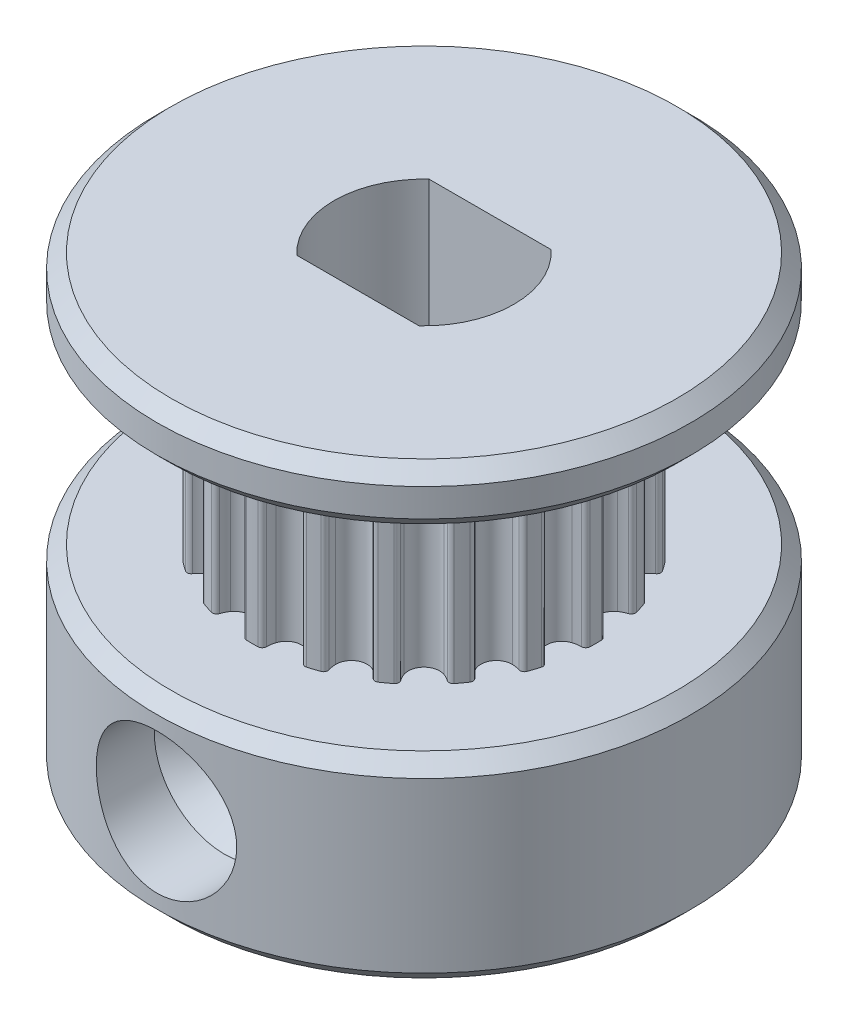
SolidWorks part; units mm, degrees
other "Markup1"
sketch "Sketch11" plane through (-10, 5.5, 10) normal (-0.2341, 0.0958, 0.9675) x (0.972, 0, 0.2351)
sketch "Sketch12" plane through (-9.5, 5.5, 9.5) normal (-0.2341, 0.0958, 0.9675) x (0.972, 0, 0.2351)
ref_plane "Front Plane" through (0, 0, 0) normal (0, 0, 1) x (1, 0, 0)
ref_plane "Top Plane" through (0, 0, 0) normal (0, 1, 0) x (1, 0, 0)
ref_plane "Right Plane" through (0, 0, 0) normal (1, 0, 0) x (0, 0, -1)
sketch "Sketch1" plane through (0, 0, 0) normal (0, 1, 0) x (1, 0, 0)
  line L0 (0, 0) -> (0, 6.3662) construction
  line L2 (0, 0) -> (0.9236, 5.8314) construction
  line L3 (0, 0) -> (1.4053, 6.2092) construction
  line L4 (1.3492, 5.9614) -> (1.2615, 5.4076) construction
  circle A0 centre (0, 0) radius 6.3662
  arc A1 (0.3928, 5.6692) -> (0.8368, 5.2832) centre (0.9236, 5.8314) ccw
  arc A2 (0.3492, 5.9592) -> (0.2042, 6.1088) centre (0.1992, 5.9589) ccw
  arc A3 (0.3492, 5.9592) -> (0.3928, 5.6692) centre (1.3492, 5.9614) ccw
  arc A4 (-0.3928, 5.6692) -> (-0.8368, 5.2832) centre (-0.9236, 5.8314) cw
  arc A5 (0.2042, 6.1088) -> (-0.2042, 6.1088) centre (0, 0) ccw
  arc A6 (-0.3492, 5.9592) -> (-0.3928, 5.6692) centre (-1.3492, 5.9614) cw
  arc A7 (-0.3492, 5.9592) -> (-0.2042, 6.1088) centre (-0.1992, 5.9589) cw
  arc A8 (1.3783, 5.5132) -> (0.8368, 5.2832) centre (0.9236, 5.8314) cw
  arc A9 (1.5094, 5.7754) -> (1.3783, 5.5132) centre (0.559, 6.0866) cw
  arc A10 (1.5094, 5.7754) -> (1.6935, 5.8729) centre (1.652, 5.7288) cw
  arc A11 (2.0819, 5.7467) -> (1.6935, 5.8729) centre (0, 0) ccw
  arc A12 (2.1736, 5.5596) -> (2.0819, 5.7467) centre (2.0308, 5.6057) ccw
  arc A13 (2.1736, 5.5596) -> (2.1255, 5.2704) centre (3.1253, 5.2527) ccw
  arc A14 (2.1255, 5.2704) -> (2.4284, 4.7661) centre (2.6804, 5.2606) ccw
  arc A15 (3.0145, 4.8174) -> (2.4284, 4.7661) centre (2.6804, 5.2606) cw
  arc A16 (3.2202, 5.0263) -> (3.0145, 4.8174) centre (2.4125, 5.6159) cw
  arc A17 (3.2202, 5.0263) -> (3.4255, 5.0621) centre (3.3414, 4.9379) cw
  arc A18 (3.7559, 4.8221) -> (3.4255, 5.0621) centre (0, 0) ccw
  arc A19 (3.7852, 4.6159) -> (3.7559, 4.8221) centre (3.6637, 4.7037) ccw
  arc A20 (3.7852, 4.6159) -> (3.6501, 4.3556) centre (4.5956, 4.0299) ccw
  arc A21 (3.6501, 4.3556) -> (3.7824, 3.7824) centre (4.1748, 4.1748) ccw
  arc A22 (4.3556, 3.6501) -> (3.7824, 3.7824) centre (4.1748, 4.1748) cw
  arc A23 (4.6159, 3.7852) -> (4.3556, 3.6501) centre (4.0299, 4.5956) cw
  arc A24 (4.6159, 3.7852) -> (4.8221, 3.7559) centre (4.7037, 3.6637) cw
  arc A25 (5.0621, 3.4255) -> (4.8221, 3.7559) centre (0, 0) ccw
  arc A26 (5.0263, 3.2202) -> (5.0621, 3.4255) centre (4.9379, 3.3414) ccw
  arc A27 (5.0263, 3.2202) -> (4.8174, 3.0145) centre (5.6159, 2.4125) ccw
  arc A28 (4.8174, 3.0145) -> (4.7661, 2.4284) centre (5.2606, 2.6804) ccw
  arc A29 (5.2704, 2.1255) -> (4.7661, 2.4284) centre (5.2606, 2.6804) cw
  arc A30 (5.5596, 2.1736) -> (5.2704, 2.1255) centre (5.2527, 3.1253) cw
  arc A31 (5.5596, 2.1736) -> (5.7467, 2.0819) centre (5.6057, 2.0308) cw
  arc A32 (5.8729, 1.6935) -> (5.7467, 2.0819) centre (0, 0) ccw
  arc A33 (5.7754, 1.5094) -> (5.8729, 1.6935) centre (5.7288, 1.652) ccw
  arc A34 (5.7754, 1.5094) -> (5.5132, 1.3783) centre (6.0866, 0.559) ccw
  arc A35 (5.5132, 1.3783) -> (5.2832, 0.8368) centre (5.8314, 0.9236) ccw
  arc A36 (5.6692, 0.3928) -> (5.2832, 0.8368) centre (5.8314, 0.9236) cw
  arc A37 (5.9592, 0.3492) -> (5.6692, 0.3928) centre (5.9614, 1.3492) cw
  arc A38 (5.9592, 0.3492) -> (6.1088, 0.2042) centre (5.9589, 0.1992) cw
  arc A39 (6.1088, -0.2042) -> (6.1088, 0.2042) centre (0, 0) ccw
  arc A40 (5.9592, -0.3492) -> (6.1088, -0.2042) centre (5.9589, -0.1992) ccw
  arc A41 (5.9592, -0.3492) -> (5.6692, -0.3928) centre (5.9614, -1.3492) ccw
  arc A42 (5.6692, -0.3928) -> (5.2832, -0.8368) centre (5.8314, -0.9236) ccw
  arc A43 (5.5132, -1.3783) -> (5.2832, -0.8368) centre (5.8314, -0.9236) cw
  arc A44 (5.7754, -1.5094) -> (5.5132, -1.3783) centre (6.0866, -0.559) cw
  arc A45 (5.7754, -1.5094) -> (5.8729, -1.6935) centre (5.7288, -1.652) cw
  arc A46 (5.7467, -2.0819) -> (5.8729, -1.6935) centre (0, 0) ccw
  arc A47 (5.5596, -2.1736) -> (5.7467, -2.0819) centre (5.6057, -2.0308) ccw
  arc A48 (5.5596, -2.1736) -> (5.2704, -2.1255) centre (5.2527, -3.1253) ccw
  arc A49 (5.2704, -2.1255) -> (4.7661, -2.4284) centre (5.2606, -2.6804) ccw
  arc A50 (4.8174, -3.0145) -> (4.7661, -2.4284) centre (5.2606, -2.6804) cw
  arc A51 (5.0263, -3.2202) -> (4.8174, -3.0145) centre (5.6159, -2.4125) cw
  arc A52 (5.0263, -3.2202) -> (5.0621, -3.4255) centre (4.9379, -3.3414) cw
  arc A53 (4.8221, -3.7559) -> (5.0621, -3.4255) centre (0, 0) ccw
  arc A54 (4.6159, -3.7852) -> (4.8221, -3.7559) centre (4.7037, -3.6637) ccw
  arc A55 (4.6159, -3.7852) -> (4.3556, -3.6501) centre (4.0299, -4.5956) ccw
  arc A56 (4.3556, -3.6501) -> (3.7824, -3.7824) centre (4.1748, -4.1748) ccw
  arc A57 (3.6501, -4.3556) -> (3.7824, -3.7824) centre (4.1748, -4.1748) cw
  arc A58 (3.7852, -4.6159) -> (3.6501, -4.3556) centre (4.5956, -4.0299) cw
  arc A59 (3.7852, -4.6159) -> (3.7559, -4.8221) centre (3.6637, -4.7037) cw
  arc A60 (3.4255, -5.0621) -> (3.7559, -4.8221) centre (0, 0) ccw
  arc A61 (3.2202, -5.0263) -> (3.4255, -5.0621) centre (3.3414, -4.9379) ccw
  arc A62 (3.2202, -5.0263) -> (3.0145, -4.8174) centre (2.4125, -5.6159) ccw
  arc A63 (3.0145, -4.8174) -> (2.4284, -4.7661) centre (2.6804, -5.2606) ccw
  arc A64 (2.1255, -5.2704) -> (2.4284, -4.7661) centre (2.6804, -5.2606) cw
  arc A65 (2.1736, -5.5596) -> (2.1255, -5.2704) centre (3.1253, -5.2527) cw
  arc A66 (2.1736, -5.5596) -> (2.0819, -5.7467) centre (2.0308, -5.6057) cw
  arc A67 (1.6935, -5.8729) -> (2.0819, -5.7467) centre (0, 0) ccw
  arc A68 (1.5094, -5.7754) -> (1.6935, -5.8729) centre (1.652, -5.7288) ccw
  arc A69 (1.5094, -5.7754) -> (1.3783, -5.5132) centre (0.559, -6.0866) ccw
  arc A70 (1.3783, -5.5132) -> (0.8368, -5.2832) centre (0.9236, -5.8314) ccw
  arc A71 (0.3928, -5.6692) -> (0.8368, -5.2832) centre (0.9236, -5.8314) cw
  arc A72 (0.3492, -5.9592) -> (0.3928, -5.6692) centre (1.3492, -5.9614) cw
  arc A73 (0.3492, -5.9592) -> (0.2042, -6.1088) centre (0.1992, -5.9589) cw
  arc A74 (-0.2042, -6.1088) -> (0.2042, -6.1088) centre (0, 0) ccw
  arc A75 (-0.3492, -5.9592) -> (-0.2042, -6.1088) centre (-0.1992, -5.9589) ccw
  arc A76 (-0.3492, -5.9592) -> (-0.3928, -5.6692) centre (-1.3492, -5.9614) ccw
  arc A77 (-0.3928, -5.6692) -> (-0.8368, -5.2832) centre (-0.9236, -5.8314) ccw
  arc A78 (-1.3783, -5.5132) -> (-0.8368, -5.2832) centre (-0.9236, -5.8314) cw
  arc A79 (-1.5094, -5.7754) -> (-1.3783, -5.5132) centre (-0.559, -6.0866) cw
  arc A80 (-1.5094, -5.7754) -> (-1.6935, -5.8729) centre (-1.652, -5.7288) cw
  arc A81 (-2.0819, -5.7467) -> (-1.6935, -5.8729) centre (0, 0) ccw
  arc A82 (-2.1736, -5.5596) -> (-2.0819, -5.7467) centre (-2.0308, -5.6057) ccw
  arc A83 (-2.1736, -5.5596) -> (-2.1255, -5.2704) centre (-3.1253, -5.2527) ccw
  arc A84 (-2.1255, -5.2704) -> (-2.4284, -4.7661) centre (-2.6804, -5.2606) ccw
  arc A85 (-3.0145, -4.8174) -> (-2.4284, -4.7661) centre (-2.6804, -5.2606) cw
  arc A86 (-3.2202, -5.0263) -> (-3.0145, -4.8174) centre (-2.4125, -5.6159) cw
  arc A87 (-3.2202, -5.0263) -> (-3.4255, -5.0621) centre (-3.3414, -4.9379) cw
  arc A88 (-3.7559, -4.8221) -> (-3.4255, -5.0621) centre (0, 0) ccw
  arc A89 (-3.7852, -4.6159) -> (-3.7559, -4.8221) centre (-3.6637, -4.7037) ccw
  arc A90 (-3.7852, -4.6159) -> (-3.6501, -4.3556) centre (-4.5956, -4.0299) ccw
  arc A91 (-3.6501, -4.3556) -> (-3.7824, -3.7824) centre (-4.1748, -4.1748) ccw
  arc A92 (-4.3556, -3.6501) -> (-3.7824, -3.7824) centre (-4.1748, -4.1748) cw
  arc A93 (-4.6159, -3.7852) -> (-4.3556, -3.6501) centre (-4.0299, -4.5956) cw
  arc A94 (-4.6159, -3.7852) -> (-4.8221, -3.7559) centre (-4.7037, -3.6637) cw
  arc A95 (-5.0621, -3.4255) -> (-4.8221, -3.7559) centre (0, 0) ccw
  arc A96 (-5.0263, -3.2202) -> (-5.0621, -3.4255) centre (-4.9379, -3.3414) ccw
  arc A97 (-5.0263, -3.2202) -> (-4.8174, -3.0145) centre (-5.6159, -2.4125) ccw
  arc A98 (-4.8174, -3.0145) -> (-4.7661, -2.4284) centre (-5.2606, -2.6804) ccw
  arc A99 (-5.2704, -2.1255) -> (-4.7661, -2.4284) centre (-5.2606, -2.6804) cw
  arc A100 (-5.5596, -2.1736) -> (-5.2704, -2.1255) centre (-5.2527, -3.1253) cw
  arc A101 (-5.5596, -2.1736) -> (-5.7467, -2.0819) centre (-5.6057, -2.0308) cw
  arc A102 (-5.8729, -1.6935) -> (-5.7467, -2.0819) centre (0, 0) ccw
  arc A103 (-5.7754, -1.5094) -> (-5.8729, -1.6935) centre (-5.7288, -1.652) ccw
  arc A104 (-5.7754, -1.5094) -> (-5.5132, -1.3783) centre (-6.0866, -0.559) ccw
  arc A105 (-5.5132, -1.3783) -> (-5.2832, -0.8368) centre (-5.8314, -0.9236) ccw
  arc A106 (-5.6692, -0.3928) -> (-5.2832, -0.8368) centre (-5.8314, -0.9236) cw
  arc A107 (-5.9592, -0.3492) -> (-5.6692, -0.3928) centre (-5.9614, -1.3492) cw
  arc A108 (-5.9592, -0.3492) -> (-6.1088, -0.2042) centre (-5.9589, -0.1992) cw
  arc A109 (-6.1088, 0.2042) -> (-6.1088, -0.2042) centre (0, 0) ccw
  arc A110 (-5.9592, 0.3492) -> (-6.1088, 0.2042) centre (-5.9589, 0.1992) ccw
  arc A111 (-5.9592, 0.3492) -> (-5.6692, 0.3928) centre (-5.9614, 1.3492) ccw
  arc A112 (-5.6692, 0.3928) -> (-5.2832, 0.8368) centre (-5.8314, 0.9236) ccw
  arc A113 (-5.5132, 1.3783) -> (-5.2832, 0.8368) centre (-5.8314, 0.9236) cw
  arc A114 (-5.7754, 1.5094) -> (-5.5132, 1.3783) centre (-6.0866, 0.559) cw
  arc A115 (-5.7754, 1.5094) -> (-5.8729, 1.6935) centre (-5.7288, 1.652) cw
  arc A116 (-5.7467, 2.0819) -> (-5.8729, 1.6935) centre (0, 0) ccw
  arc A117 (-5.5596, 2.1736) -> (-5.7467, 2.0819) centre (-5.6057, 2.0308) ccw
  arc A118 (-5.5596, 2.1736) -> (-5.2704, 2.1255) centre (-5.2527, 3.1253) ccw
  arc A119 (-5.2704, 2.1255) -> (-4.7661, 2.4284) centre (-5.2606, 2.6804) ccw
  arc A120 (-4.8174, 3.0145) -> (-4.7661, 2.4284) centre (-5.2606, 2.6804) cw
  arc A121 (-5.0263, 3.2202) -> (-4.8174, 3.0145) centre (-5.6159, 2.4125) cw
  arc A122 (-5.0263, 3.2202) -> (-5.0621, 3.4255) centre (-4.9379, 3.3414) cw
  arc A123 (-4.8221, 3.7559) -> (-5.0621, 3.4255) centre (0, 0) ccw
  arc A124 (-4.6159, 3.7852) -> (-4.8221, 3.7559) centre (-4.7037, 3.6637) ccw
  arc A125 (-4.6159, 3.7852) -> (-4.3556, 3.6501) centre (-4.0299, 4.5956) ccw
  arc A126 (-4.3556, 3.6501) -> (-3.7824, 3.7824) centre (-4.1748, 4.1748) ccw
  arc A127 (-3.6501, 4.3556) -> (-3.7824, 3.7824) centre (-4.1748, 4.1748) cw
  arc A128 (-3.7852, 4.6159) -> (-3.6501, 4.3556) centre (-4.5956, 4.0299) cw
  arc A129 (-3.7852, 4.6159) -> (-3.7559, 4.8221) centre (-3.6637, 4.7037) cw
  arc A130 (-3.4255, 5.0621) -> (-3.7559, 4.8221) centre (0, 0) ccw
  arc A131 (-3.2202, 5.0263) -> (-3.4255, 5.0621) centre (-3.3414, 4.9379) ccw
  arc A132 (-3.2202, 5.0263) -> (-3.0145, 4.8174) centre (-2.4125, 5.6159) ccw
  arc A133 (-3.0145, 4.8174) -> (-2.4284, 4.7661) centre (-2.6804, 5.2606) ccw
  arc A134 (-2.1255, 5.2704) -> (-2.4284, 4.7661) centre (-2.6804, 5.2606) cw
  arc A135 (-2.1736, 5.5596) -> (-2.1255, 5.2704) centre (-3.1253, 5.2527) cw
  arc A136 (-2.1736, 5.5596) -> (-2.0819, 5.7467) centre (-2.0308, 5.6057) cw
  arc A137 (-1.6935, 5.8729) -> (-2.0819, 5.7467) centre (0, 0) ccw
  arc A138 (-1.5094, 5.7754) -> (-1.6935, 5.8729) centre (-1.652, 5.7288) ccw
  arc A139 (-1.5094, 5.7754) -> (-1.3783, 5.5132) centre (-0.559, 6.0866) ccw
  arc A140 (-1.3783, 5.5132) -> (-0.8368, 5.2832) centre (-0.9236, 5.8314) ccw
  point P4 (0, 6.1122)
  point P11 (0, 6.3662)
  point P67 (0, 0)
  dimension "D1" = 12.7324
  dimension "D3" = 1
  dimension "D4" = 0.555
  dimension "D2" = 0.15
  dimension "D5" = 0.4
  dimension "D8" = 0.254
  dimension "D7" = 9
  dimension "D6" = 0.254
  dimension "D9" = 20
extrude "Gear" add sketch "Sketch1" along normal mid plane 7 contours A140 A139 A138 A137 A136 A135 A134 A133 A132 A131 A130 A129 A128 A127 A126 A125 A124 A123 A122 A121 A120 A119 A118 A117 A116 A115 A114 A113 A112 A111 A110 A109 A108 A107 A106 A105 A104 A103 A102 A101 A100 A99 A98 A97 A96 A95 A94 A93 A92 A91 A90 region at (0, 0, 0)
sketch "Sketch2" plane through (0, -3.5, 0) normal (0, -1, 0) x (1, 0, 0)
  line L0 (-11.7249, 0) -> (11.7249, 0) construction
  line L1 (-1.9666, 1.85) -> (1.9666, 1.85)
  line L2 (-1.9666, -1.85) -> (1.9666, -1.85)
  line L3 (-2.172, -2.35) -> (2.172, -2.35)
  line L4 (-2.172, 2.35) -> (2.172, 2.35)
  arc A0 (-1.9666, 1.85) -> (-1.9666, -1.85) centre (0, 0) ccw
  arc A1 (1.9666, -1.85) -> (1.9666, 1.85) centre (0, 0) ccw
  arc A2 (2.172, -2.35) -> (2.172, 2.35) centre (0, 0) ccw
  arc A3 (-2.172, 2.35) -> (-2.172, -2.35) centre (0, 0) ccw
  circle A4 centre (0, 0) radius 9.5
  point P4 (0, 0)
  dimension "D2" = 5.4
  dimension "D4" = 19
  dimension "D1" = 3.7
  dimension "D3" = 0.5
extrude "Base" add sketch "Sketch2" along normal blind 7 contours A4 L0 A3 L4 A2 | L0 A4 A2 L3 A3 region at (0, -3.5, 4.3409) region at (0, -3.5, -4.3409)
sketch "Sketch3" plane through (0, 0, 0) normal (0, 0, 1) x (1, 0, 0)
  line L0 (0, 0) -> (0, -7) construction
  line L1 (0, -10.06) -> (2.65, -8.53)
  line L2 (2.65, -8.53) -> (2.65, -5.47)
  line L3 (2.65, -5.47) -> (0, -3.94)
  line L4 (0, -3.94) -> (-2.65, -5.47)
  line L5 (-2.65, -5.47) -> (-2.65, -8.53)
  line L6 (-2.65, -8.53) -> (0, -10.06)
  line L7 (-2.65, -8.53) -> (-2.65, -10.5)
  line L8 (-9.5, -10.5) -> (9.5, -10.5) construction
  line L9 (-2.65, -10.5) -> (2.65, -10.5)
  line L10 (2.65, -10.5) -> (2.65, -8.53)
  circle A0 centre (0, -7) radius 2.65 construction
  dimension "D1" = 5.3
  dimension "D2" = 7
extrude "Nut Passthrough" cut sketch "Sketch3" along normal blind 4.5 contours L9 L10 L1 L6 L7 | L5 L6 L1 L2 L3 L4 region at (0, -7, 0) region at (1.3533, -9.3439, 0)
sketch "Sketch9" plane through (0, 3.5, 0) normal (0, 1, 0) x (1, 0, 0)
  circle A0 centre (0, 0) radius 9.5
  dimension "D1" = 19
extrude "Top" add sketch "Sketch9" along normal blind 2
extrude "Shaft Hole" cut sketch "Sketch2<4>" against normal through all contours A0 L0 A1 L1 | L0 A0 L2 A1 | L0 A3 L3 A2 A1 L2 A0 | A3 L0 A0 L1 A1 A2 L4 region at (-2.8693, -3.5, 1.2552) region at (-2.95, -3.5, -0.0682) region at (0, -3.5, 0.8808) region at (0, -3.5, -0.8808)
sketch "Sketch2<4>" plane through (0, -3.5, 0) normal (0, -1, 0) x (1, 0, 0) same geometry as "Sketch2"
extrude "Boss-Extrude4" add sketch "Sketch2<5>" along normal blind 7 separate body contours L0 A0 L2 A1 | A0 L0 A1 L1 region at (0, -3.5, 0.8808) region at (0, -3.5, -0.8808)
sketch "Sketch2<5>" plane through (0, -3.5, 0) normal (0, -1, 0) x (1, 0, 0) same geometry as "Sketch2"
sketch "Sketch10" plane through (0, 0, 0) normal (0, 0, 1) x (1, 0, 0)
  circle A0 centre (0, -7) radius 1.4
  circle A1 centre (0, -7) radius 2.5
  dimension "D1" = 2.8
  dimension "D2" = 5
extrude "Screw Hole" cut sketch "Sketch10" along normal through all contours A0 region at (0, -7, 0)
extrude "Screw Counterbore" cut sketch "Sketch10<3>" along normal through all from offset 6
sketch "Sketch10<3>" plane through (0, 0, 0) normal (0, 0, 1) x (1, 0, 0) same geometry as "Sketch10"
chamfer "Chamfer1" distance 0.5 angle 45 4 edges at (0, -3.5, -9.5) (0, -10.5, -9.5) (0, 3.5, 9.5) (0, 5.5, 9.5)
chamfer "Chamfer2" distance 1.1 angle 45 1 edges at (2.5, -7, 6)
equation "\"D1@Sketch1\"=\"pd\""
equation "\"teethNum\"= 20"
equation "\"pitch\"= 2mm"
equation "\"pd\"= \"teethNum\" * \"pitch\" / PI"
equation "\"D9@Sketch1\"=\"teethNum\""
equation "\"outerDia\"= 19"
equation "\"D4@Sketch2\"=\"outerDia\""
equation "\"D1@Sketch9\"=\"outerDia\""
